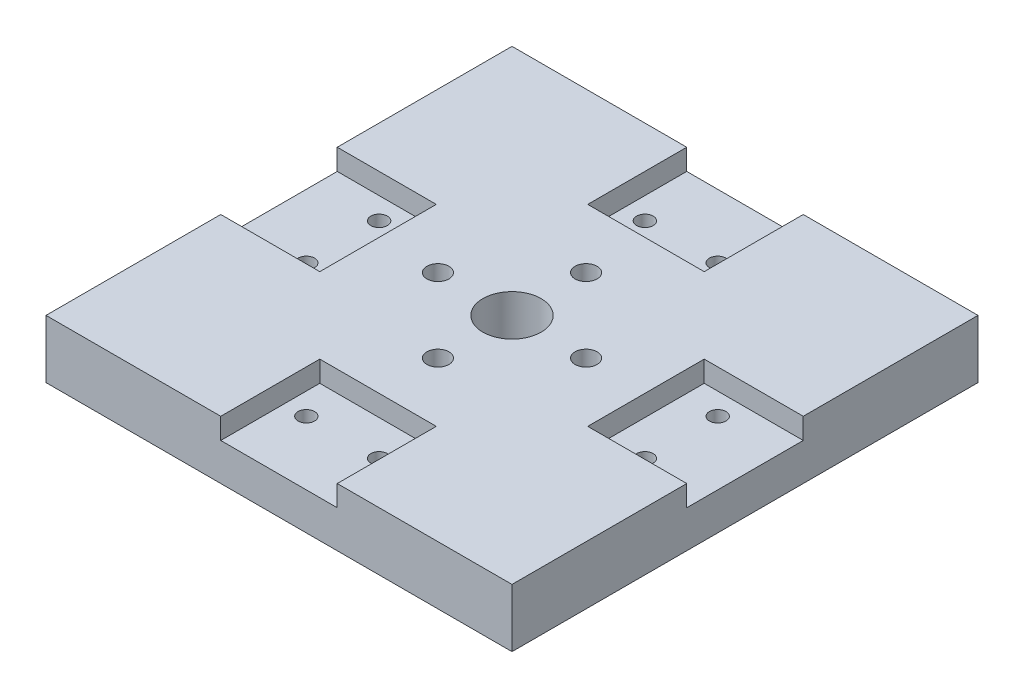
SolidWorks part; units mm, degrees
material "6061 Alloy"
ref_plane "Front Plane" through (0, 0, 0) normal (0, 0, 1) x (1, 0, 0)
ref_plane "Top Plane" through (0, 0, 0) normal (0, 1, 0) x (1, 0, 0)
ref_plane "Right Plane" through (0, 0, 0) normal (1, 0, 0) x (0, 0, -1)
sketch "Sketch1" plane through (0, 0, 0) normal (0, 1, 0) x (1, 0, 0)
  line L1 (0, 0) -> (101.6, 0)
  line L2 (0, 0) -> (0, 101.6)
  line L3 (0, 101.6) -> (101.6, 101.6)
  line L4 (101.6, 0) -> (101.6, 101.6)
  dimension "D1" = 101.6
  dimension "D2" = 101.6
extrude "Boss-Extrude1" add sketch "Sketch1" along normal blind 12.7
sketch "Sketch2" plane through (0, 12.7, 0) normal (0, 1, 0) x (1, 0, 0)
  line L0 (101.6, 101.6) -> (0, 101.6) construction
  line L1 (38.1, 101.6) -> (63.5, 101.6)
  line L2 (38.1, 101.6) -> (38.1, 80.01)
  line L3 (38.1, 80.01) -> (63.5, 80.01)
  line L4 (63.5, 101.6) -> (63.5, 80.01)
  line L5 (0, 101.6) -> (0, 0) construction
  line L6 (0, 63.5) -> (21.59, 63.5)
  line L7 (0, 63.5) -> (0, 38.1)
  line L8 (0, 38.1) -> (21.59, 38.1)
  line L9 (21.59, 63.5) -> (21.59, 38.1)
  line L10 (0, 0) -> (101.6, 0) construction
  line L11 (38.1, 0) -> (63.5, 0)
  line L12 (38.1, 0) -> (38.1, 21.59)
  line L13 (38.1, 21.59) -> (63.5, 21.59)
  line L14 (63.5, 0) -> (63.5, 21.59)
  line L15 (101.6, 0) -> (101.6, 101.6) construction
  line L16 (101.6, 63.5) -> (80.01, 63.5)
  line L17 (101.6, 63.5) -> (101.6, 38.1)
  line L18 (101.6, 38.1) -> (80.01, 38.1)
  line L19 (80.01, 63.5) -> (80.01, 38.1)
  dimension "D1" = 38.1
  dimension "D2" = 25.4
  dimension "D3" = 25.4
  dimension "D4" = 38.1
  dimension "D5" = 25.4
  dimension "D6" = 38.1
  dimension "D7" = 25.4
  dimension "D8" = 38.1
  dimension "D9" = 21.59
  dimension "D10" = 21.59
  dimension "D11" = 21.59
  dimension "D12" = 21.59
extrude "Cut-Extrude1" cut sketch "Sketch2" against normal blind 4.572
sketch "Sketch3" plane through (0, 12.7, 0) normal (0, 1, 0) x (1, 0, 0)
  line L0 (38.1, 101.6) -> (0, 101.6) construction
  line L1 (20.6375, 80.9625) -> (80.9625, 80.9625)
  line L2 (20.6375, 80.9625) -> (20.6375, 20.6375)
  line L3 (20.6375, 20.6375) -> (80.9625, 20.6375)
  line L4 (80.9625, 80.9625) -> (80.9625, 20.6375)
  line L5 (0, 38.1) -> (0, 0) construction
  circle A0 centre (34.6507, 50.8) radius 2.4
  circle A1 centre (50.8, 66.9493) radius 2.4
  circle A2 centre (66.9493, 50.8) radius 2.4
  circle A3 centre (50.8, 34.6507) radius 2.4
  dimension "D5" = 4.8
  dimension "D6" = 4.8
  dimension "D7" = 4.8
  dimension "D8" = 4.8
  dimension "D1" = 60.325
  dimension "D2" = 60.325
  dimension "D3" = 20.6375
  dimension "D4" = 20.6375
  dimension "D9" = 14.0132
  dimension "D10" = 14.0132
  dimension "D11" = 14.0132
  dimension "D12" = 14.0132
  dimension "D13" = 30.1625
  dimension "D14" = 30.1625
  dimension "D15" = 30.1625
  dimension "D16" = 30.1625
extrude "Cut-Extrude2" cut sketch "Sketch3" against normal through all contours A2 | A1 | A0 | A3
sketch "Sketch4" plane through (0, 8.128, 0) normal (0, 1, 0) x (1, 0, 0)
  line L0 (0, 63.5) -> (0, 38.1) construction
  line L1 (63.5, 101.6) -> (38.1, 101.6) construction
  line L2 (101.6, 38.1) -> (101.6, 63.5) construction
  line L3 (38.1, 0) -> (63.5, 0) construction
  line L4 (0, 38.1) -> (21.59, 38.1) construction
  line L5 (38.1, 21.59) -> (38.1, 0) construction
  line L6 (80.01, 38.1) -> (101.6, 38.1) construction
  line L7 (63.5, 80.01) -> (63.5, 101.6) construction
  circle A0 centre (87.7062, 58.7375) radius 1.8034
  circle A1 centre (87.7062, 42.8625) radius 1.8034
  circle A2 centre (58.7375, 87.7062) radius 1.8034
  circle A3 centre (42.8625, 87.7062) radius 1.8034
  circle A4 centre (13.8938, 58.7375) radius 1.8034
  circle A5 centre (13.8938, 42.8625) radius 1.8034
  circle A6 centre (42.8625, 13.8938) radius 1.8034
  circle A7 centre (58.7375, 13.8938) radius 1.8034
  dimension "D1" = 3.6068
  dimension "D2" = 3.6068
  dimension "D3" = 3.6068
  dimension "D4" = 3.6068
  dimension "D5" = 3.6068
  dimension "D6" = 3.6068
  dimension "D7" = 3.6068
  dimension "D8" = 3.6068
  dimension "D9" = 13.8938
  dimension "D10" = 13.8938
  dimension "D11" = 13.8938
  dimension "D12" = 13.8938
  dimension "D13" = 13.8938
  dimension "D14" = 13.8938
  dimension "D15" = 13.8938
  dimension "D16" = 13.8938
  dimension "D17" = 15.875
  dimension "D18" = 4.7625
  dimension "D19" = 4.7625
  dimension "D20" = 15.875
  dimension "D21" = 4.7625
  dimension "D22" = 15.875
  dimension "D23" = 4.7625
  dimension "D24" = 15.875
extrude "Cut-Extrude3" cut sketch "Sketch4" against normal through all
sketch "Sketch5" plane through (0, 12.7, 0) normal (0, 1, 0) x (1, 0, 0)
  line L0 (101.6, 101.6) -> (63.5, 101.6) construction
  line L1 (101.6, 38.1) -> (101.6, 63.5) construction
  circle A0 centre (50.8, 50.8) radius 6.35
  dimension "D1" = 12.7
  dimension "D2" = 50.8
  dimension "D3" = 50.8
extrude "Cut-Extrude4" cut sketch "Sketch5" against normal through all
equation "\"hinge_hole\"= 0.142in"
equation "\"D1@Sketch4\"=\"hinge_hole\""
equation "\"D2@Sketch4\"=\"hinge_hole\""
equation "\"D3@Sketch4\"=\"hinge_hole\""
equation "\"D4@Sketch4\"=\"hinge_hole\""
equation "\"D5@Sketch4\"=\"hinge_hole\""
equation "\"D6@Sketch4\"=\"hinge_hole\""
equation "\"D7@Sketch4\"=\"hinge_hole\""
equation "\"D8@Sketch4\"=\"hinge_hole\""
equation "\"hinge_hole_dist\"= 0.297 + 0.25"
equation "\"D9@Sketch4\"=\"hinge_hole_dist\""
equation "\"D10@Sketch4\"=\"hinge_hole_dist\""
equation "\"D11@Sketch4\"=\"hinge_hole_dist\""
equation "\"D12@Sketch4\"=\"hinge_hole_dist\""
equation "\"D13@Sketch4\"=\"hinge_hole_dist\""
equation "\"D14@Sketch4\"=\"hinge_hole_dist\""
equation "\"D15@Sketch4\"=\"hinge_hole_dist\""
equation "\"D16@Sketch4\"=\"hinge_hole_dist\""
equation "\"hinge_hole_sep\"= 0.625"
equation "\"hinge_hole_from_wall\"= ( 1 - \"hinge_hole_sep\" ) / 2"
equation "\"D17@Sketch4\"=\"hinge_hole_sep\""
equation "\"D18@Sketch4\"=\"hinge_hole_from_wall\""
equation "\"D19@Sketch4\"=\"hinge_hole_from_wall\""
equation "\"D20@Sketch4\"=\"hinge_hole_sep\""
equation "\"D21@Sketch4\"=\"hinge_hole_from_wall\""
equation "\"D22@Sketch4\"=\"hinge_hole_sep\""
equation "\"D23@Sketch4\"=\"hinge_hole_from_wall\""
equation "\"D24@Sketch4\"=\"hinge_hole_sep\""
equation "\"D9@Sketch2\"=\"hinge_hole_dist\" + (0.6-0.297)"
equation "\"D12@Sketch2\"=\"hinge_hole_dist\" + (0.6-0.297)"
equation "\"D11@Sketch2\"=\"hinge_hole_dist\" + (0.6-0.297)"
equation "\"D10@Sketch2\"=\"hinge_hole_dist\" + (0.6-0.297)"
